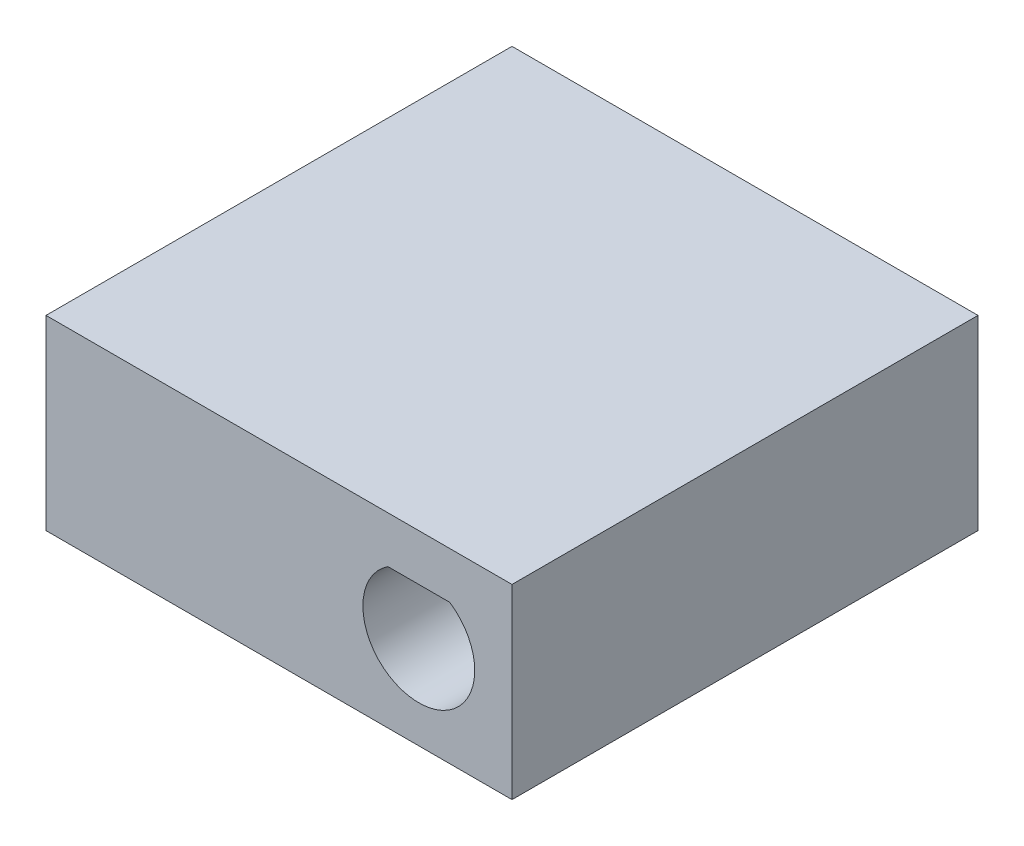
SolidWorks part; units mm, degrees
ref_plane "Front Plane" through (0, 0, 0) normal (0, 0, 1) x (1, 0, 0)
ref_plane "Top Plane" through (0, 0, 0) normal (0, 1, 0) x (1, 0, 0)
ref_plane "Right Plane" through (0, 0, 0) normal (1, 0, 0) x (0, 0, -1)
sketch "Sketch1" plane through (0, 0, 0) normal (0, 1, 0) x (1, 0, 0)
  line L1 (-12.5, -12.5) -> (12.5, -12.5)
  line L2 (-12.5, -12.5) -> (-12.5, 12.5)
  line L3 (-12.5, 12.5) -> (12.5, 12.5)
  line L4 (12.5, -12.5) -> (12.5, 12.5)
  line L5 (-12.5, -12.5) -> (12.5, 12.5) construction
  line L6 (-12.5, 12.5) -> (12.5, -12.5) construction
  point P0 (0, 0)
  dimension "D1" = 25
  dimension "D2" = 25
extrude "Boss-Extrude1" add sketch "Sketch1" along normal blind 10
sketch "Sketch2" plane through (0, 0, 12.5) normal (0, 0, 1) x (1, 0, 0)
  line L0 (12.5, 5) -> (7.5, 5) construction
  line L1 (12.5, 10) -> (12.5, 0) construction
  line L2 (7.5, 2) -> (7.5, 7.5) construction
  line L3 (5.8417, 7.5) -> (9.1583, 7.5)
  arc A0 (5.8417, 7.5) -> (9.1583, 7.5) centre (7.5, 5) ccw
  point P11 (7.5, 7.5)
  dimension "D2" = 6
  dimension "D1" = 5
  dimension "D3" = 5.5
extrude "Cut-Extrude1" cut sketch "Sketch2" against normal blind 10
